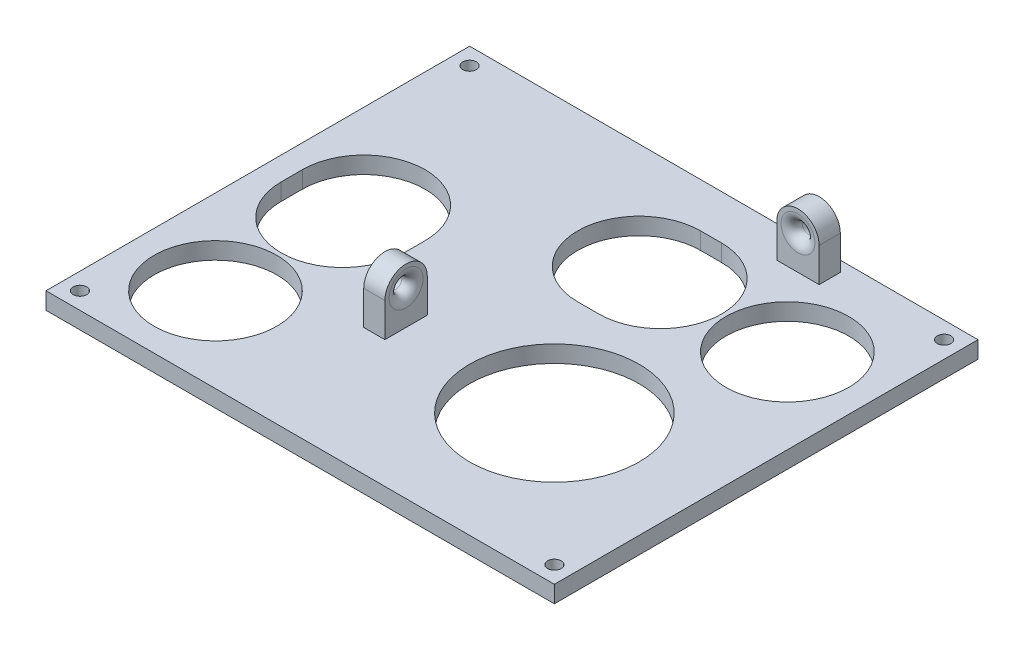
SolidWorks part; units mm, degrees
ref_plane "前视基准面" through (0, 0, 0) normal (0, 0, 1) x (1, 0, 0)
ref_plane "上视基准面" through (0, 0, 0) normal (0, 1, 0) x (1, 0, 0)
ref_plane "右视基准面" through (0, 0, 0) normal (1, 0, 0) x (0, 0, -1)
sketch "Sketch1" plane through (0, 0, 0) normal (0, 1, 0) x (1, 0, 0)
  line L1 (-60, 50) -> (60, 50)
  line L2 (-60, 50) -> (-60, -50)
  line L3 (-60, -50) -> (60, -50)
  line L4 (60, 50) -> (60, -50)
  line L5 (0, -50) -> (0, 50) construction
  line L6 (-60, 0) -> (60, 0) construction
  point P0 (0, 0)
  dimension "D1" = 120
  dimension "D2" = 100
extrude "Boss-Extrude1" add sketch "Sketch1" along normal blind 4
sketch "Sketch2" plane through (0, 4, 0) normal (0, 1, 0) x (1, 0, 0)
  line L0 (60, -50) -> (60, 50) construction
  line L1 (60, 50) -> (-60, 50) construction
  line L2 (-60, -50) -> (60, -50) construction
  line L3 (-60, 50) -> (-60, -50) construction
  line L4 (10, 25) -> (19.5, 25) construction
  line L5 (-40, 0) -> (-40, -9.5) construction
  line L6 (40, 25) -> (49.5, 25) construction
  line L8 (-40, -30) -> (-40, -39.5) construction
  circle A0 centre (40, 25) radius 14.5
  circle A1 centre (10, 25) radius 14.5
  circle A2 centre (-40, 0) radius 14.5
  circle A3 centre (-40, -30) radius 14.5
  circle A5 centre (19.5, 25) radius 1.6 construction
  circle A6 centre (49.5, 25) radius 1.6 construction
  circle A7 centre (-40, -9.5) radius 1.6 construction
  circle A8 centre (-40, -39.5) radius 1.6 construction
  circle A9 centre (10, 15.5) radius 1.6 construction
  circle A10 centre (0.5, 25) radius 1.6 construction
  circle A11 centre (10, 34.5) radius 1.6 construction
  circle A12 centre (40, 15.5) radius 1.6 construction
  circle A13 centre (30.5, 25) radius 1.6 construction
  circle A14 centre (40, 34.5) radius 1.6 construction
  circle A15 centre (-49.5, -30) radius 1.6 construction
  circle A16 centre (-40, -20.5) radius 1.6 construction
  circle A17 centre (-30.5, -30) radius 1.6 construction
  circle A19 centre (-49.5, 0) radius 1.6 construction
  circle A21 centre (-40, 9.5) radius 1.6 construction
  circle A23 centre (-30.5, 0) radius 1.6 construction
  circle A24 centre (-0.5, 0) radius 1.6 [skipped]
  circle A25 centre (-79.5, 0) radius 1.6 [skipped]
  circle A26 centre (-40, 39.5) radius 1.6 [skipped]
  point P33 (10, 25)
  point P40 (40, 25)
  point P47 (-40, -30)
  point P60 (-40, 0)
  dimension "D1" = 29
  dimension "D8" = 3.2
  dimension "D11" = 3.2
  dimension "D2" = 20
  dimension "D3" = 25
  dimension "D4" = 20
  dimension "D5" = 20
  dimension "D6" = 30
  dimension "D7" = 30
  dimension "D9" = 9.5
  dimension "D10" = 9.5
  dimension "D12" = 9.5
  dimension "D13" = 4
  dimension "D14" = 4
  dimension "D15" = 4
  dimension "D16" = 4
extrude "Cut-Extrude1" cut sketch "Sketch2" against normal blind 4
sketch "Sketch3" plane through (0, 4, 0) normal (0, 1, 0) x (1, 0, 0)
  line L0 (-40, 0) -> (-40, -30) construction
  line L2 (10, 25) -> (40, 25) construction
  line L4 (-40, -15) -> (25, -15) construction
  line L5 (25, -15) -> (25, 25) construction
  circle A0 centre (25, -15) radius 20
  circle A1 centre (25, -3.75) radius 1.6 construction
  circle A2 centre (36.25, -15) radius 1.6 construction
  circle A3 centre (25, -26.25) radius 1.6 construction
  circle A4 centre (13.75, -15) radius 1.6 construction
  point P23 (25, -15)
  dimension "D1" = 40
  dimension "D2" = 11.25
  dimension "D3" = 3.2
  dimension "D4" = 4
extrude "Cut-Extrude2" cut sketch "Sketch3" against normal blind 10
sketch "Sketch5" plane through (0, 4, 0) normal (0, 1, 0) x (1, 0, 0)
  line L0 (-60, -50) -> (60, -50) construction
  line L1 (-56, -46) -> (56, -46) construction
  line L2 (-56, -46) -> (-56, 46) construction
  line L3 (-56, 46) -> (56, 46) construction
  line L4 (56, -46) -> (56, 46) construction
  line L5 (0, 46) -> (0, -46) construction
  line L6 (-56, 0) -> (56, 0) construction
  line L7 (-60, 50) -> (-60, -50) construction
  circle A0 centre (-56, 46) radius 1.6
  circle A1 centre (56, 46) radius 1.6
  circle A2 centre (56, -46) radius 1.6
  circle A3 centre (-56, -46) radius 1.6
  point P0 (0, 0)
  dimension "D1" = 3.2
  dimension "D2" = 4
  dimension "D3" = 4
extrude "Cut-Extrude5" cut sketch "Sketch5" against normal blind 10
sketch "Sketch7" plane through (0, 4, 0) normal (0, 1, 0) x (1, 0, 0)
  line L0 (-40, 0) -> (-40, 5) construction
  line L1 (-54.5, 0) -> (-54.5, 5)
  line L2 (-25.5, 0) -> (-25.5, 5)
  line L3 (10, 25) -> (5, 25) construction
  line L4 (10, 10.5) -> (5, 10.5)
  line L5 (10, 39.5) -> (5, 39.5)
  arc A0 (-54.5, 0) -> (-25.5, 0) centre (-40, 0) ccw
  arc A1 (-25.5, 5) -> (-54.5, 5) centre (-40, 5) ccw
  arc A2 (10, 10.5) -> (10, 39.5) centre (10, 25) ccw
  arc A3 (5, 39.5) -> (5, 10.5) centre (5, 25) ccw
  circle A4 centre (-40, 0) radius 14.5 construction
  point P3 (-40, 2.5)
  point P10 (7.5, 25)
  dimension "D1" = 5
extrude "Cut-Extrude6" cut sketch "Sketch7" against normal blind 10
sketch "Sketch8" plane through (0, 4, 0) normal (0, 1, 0) x (1, 0, 0)
  line L0 (-40, -30) -> (-40, 0) construction
  line L2 (10, 25) -> (40, 25) construction
  line L3 (-15, -10) -> (-10, -10)
  line L4 (-15, -10) -> (-15, -20)
  line L5 (-15, -20) -> (-10, -20)
  line L6 (-10, -10) -> (-10, -20)
  line L7 (-12.5, -20) -> (-12.5, -10) construction
  line L8 (-15, -15) -> (-10, -15) construction
  line L9 (20, 47.5) -> (30, 47.5)
  line L10 (20, 47.5) -> (20, 42.5)
  line L11 (20, 42.5) -> (30, 42.5)
  line L12 (30, 47.5) -> (30, 42.5)
  line L13 (25, 42.5) -> (25, 47.5) construction
  line L14 (20, 45) -> (30, 45) construction
  point P4 (-12.5, -15)
  point P12 (25, 45)
  point P20 (-40, -15)
  point P22 (25, 25)
  dimension "D1" = 5
  dimension "D2" = 10
  dimension "D3" = 22.5
  dimension "D4" = 25
extrude "Boss-Extrude2" add sketch "Sketch8" along normal blind 14
sketch "Sketch9" plane through (0, 0, -42.5) normal (0, 0, 1) x (1, 0, 0)
  line L0 (-60, 4) -> (60, 4) construction
  line L1 (25, 18) -> (25, 12) construction
  line L2 (20, 18) -> (30, 18) construction
  line L3 (20, 18) -> (20, 4) construction
  line L4 (30, 18) -> (30, 4) construction
  line L5 (20, 12) -> (20, 22.099)
  line L6 (20, 22.099) -> (30, 22.099)
  line L7 (30, 22.099) -> (30, 12)
  circle A0 centre (25, 12) radius 1.5
  arc A1 (20, 12) -> (30, 12) centre (25, 12) cw
  dimension "D1" = 8
  dimension "D2" = 3
extrude "Cut-Extrude7" cut sketch "Sketch9" against normal through all
sketch "Sketch10" plane through (-10, 0, 0) normal (1, 0, 0) x (0, 0, -1)
  line L0 (-20, 18) -> (-20, 4) construction
  line L1 (-10, 18) -> (-10, 4) construction
  line L2 (-50, 4) -> (50, 4) construction
  line L3 (-20, 12) -> (-20, 23.5311)
  line L4 (-20, 23.5311) -> (-10, 23.5311)
  line L5 (-10, 23.5311) -> (-10, 12)
  circle A0 centre (-15, 12) radius 1.5
  arc A1 (-20, 12) -> (-10, 12) centre (-15, 12) cw
  point P13 (-15, 23.5311)
  dimension "D1" = 3
  dimension "D2" = 8
extrude "Cut-Extrude8" cut sketch "Sketch10" against normal blind 5
fillet "Fillet1" radius 2.5 4 edges at (26.5, 12, -47.5) (26.5, 12, -42.5) (-15, 12, 13.5) (-10, 12, 13.5)
equation "\"D4@Sketch2\"=\"D5@Sketch2\""
equation "\"D2@Sketch2\"=\"D5@Sketch2\""
equation "\"D3@Sketch5\"=\"D2@Sketch5\""
